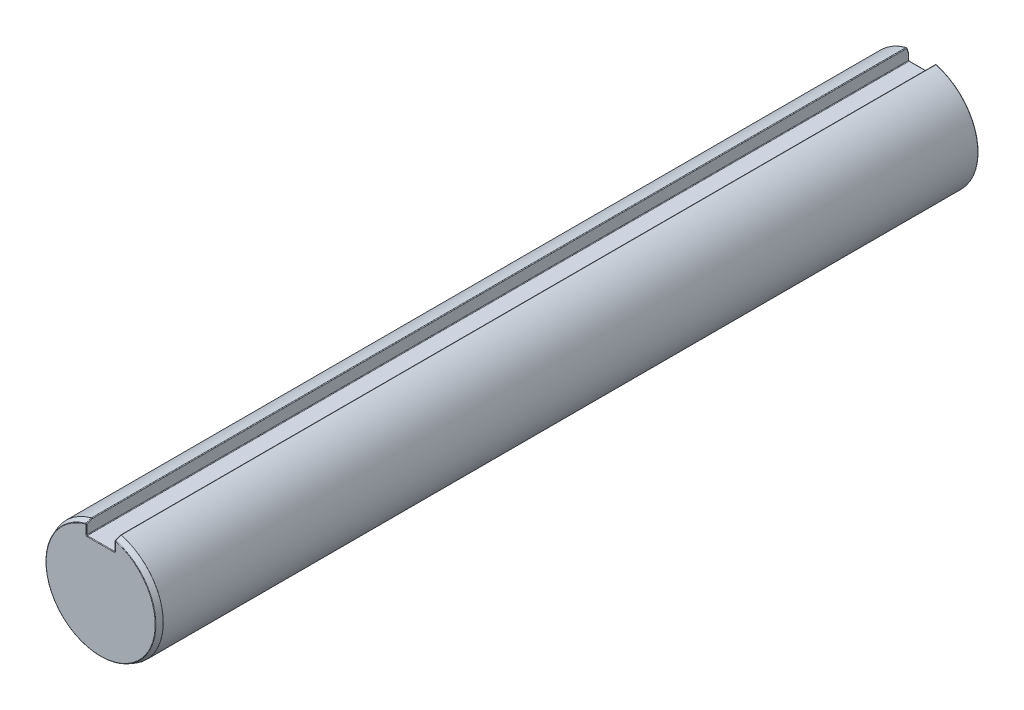
SolidWorks part; units mm, degrees
ref_plane "Front Plane" through (0, 0, 0) normal (0, 0, 1) x (1, 0, 0)
ref_plane "Top Plane" through (0, 0, 0) normal (0, 1, 0) x (1, 0, 0)
ref_plane "Right Plane" through (0, 0, 0) normal (1, 0, 0) x (0, 0, -1)
sketch "Sketch1" plane through (0, 0, 0) normal (0, 0, 1) x (1, 0, 0)
  line L1 (-1.1938, 3.5719) -> (1.1938, 3.5719)
  line L2 (-1.1938, 3.5719) -> (-1.1938, 4.7625)
  line L3 (-1.1938, 4.7625) -> (1.1938, 4.7625)
  line L4 (1.1938, 3.5719) -> (1.1938, 4.7625)
  line L5 (-1.1938, 3.5719) -> (1.1938, 4.7625) construction
  line L6 (-1.1938, 4.7625) -> (1.1938, 3.5719) construction
  circle A0 centre (0, 0) radius 4.7625
  point P3 (0, 4.1672)
  dimension "Diameter" = 9.525
  dimension "Keyway Width" = 2.3876
  dimension "Keyway Depth" = 1.1906
sketch "Sketch2" plane through (0, 0, 0) normal (1, 0, 0) x (0, 0, -1)
  line L0 (0, 4.7625) -> (0, -4.7625) construction
  line L2 (76.2, -4.7625) -> (-76.2, -4.7625)
  line L3 (76.2, -4.7625) -> (76.2, 4.7625)
  line L4 (76.2, 4.7625) -> (-76.2, 4.7625)
  line L5 (-76.2, -4.7625) -> (-76.2, 4.7625)
  line L6 (76.2, -4.7625) -> (-76.2, 4.7625) construction
  line L7 (76.2, 4.7625) -> (-76.2, -4.7625) construction
  line L8 (-76.2, -4.7625) -> (76.2, -4.7625)
  point P0 (0, 0)
  point P3 (0, 0)
  point P9 (-61.9125, -4.7625)
  point P11 (61.9125, -4.7625)
  point P15 (0, -4.7625)
  dimension "Length" = 152.4
  dimension "Keyway Length" = 152.4
  dimension "D1" = 14.2875
  dimension "D2" = 14.2875
sketch "Sketch3" plane through (0, 0, 0) normal (0, 0, 1) x (1, 0, 0)
  line L1 (-1.1938, 4.7625) -> (1.1938, 4.7625)
  line L2 (-1.1938, 4.7625) -> (-1.1938, 3.5719)
  line L3 (-1.1938, 3.5719) -> (1.1938, 3.5719)
  line L4 (1.1938, 4.7625) -> (1.1938, 3.5719)
  circle A0 centre (0, 0) radius 4.7625 construction
  circle A1 centre (0, 0) radius 4.7625
extrude "Boss-Extrude1" add sketch "Sketch3" along normal blind 27.75 and the other way blind 41.0756 contours L2 A1 L4 L3 region at (0, -0.1646, 0)
chamfer "Chamfer1" distance 0.4763 angle 20 2 edges at (0, -4.7625, -41.0756) (0, -4.7625, 27.75) first distance on face at (0, 1.7479, -41.0756) first distance on face at (0, -0.076, -6.6628)
fillet "Fillet1" radius 0.0476 18 edges at (0, -4.5892, 27.75) (0, -4.2863, -41.0756) (0, -4.7625, -40.9023) (0, -4.7625, 27.2738) (-1.1938, 4.6104, -6.8143) (1.1938, 4.6104, -6.8143) (1.1938, 3.5719, -6.6628) (-1.1938, 3.5719, -6.6628) (0, 3.5719, 27.75) (1.1938, 4.0015, 27.75) (-1.1938, 4.0015, 27.75) (0, 3.5719, -41.0756) (1.1938, 3.8443, -41.0756) (-1.1938, 3.8443, -41.0756)
equation "\"D1@Chamfer1\"=\"Diameter@Sketch1\"*.05"
equation "\"D1@Fillet1\"=\"Diameter@Sketch1\"*.005"
equation "\"D2@Sketch2\"=\"D1@Sketch2\""
equation "\"D1@Sketch2\"=\"Diameter@Sketch1\"*1.5"
